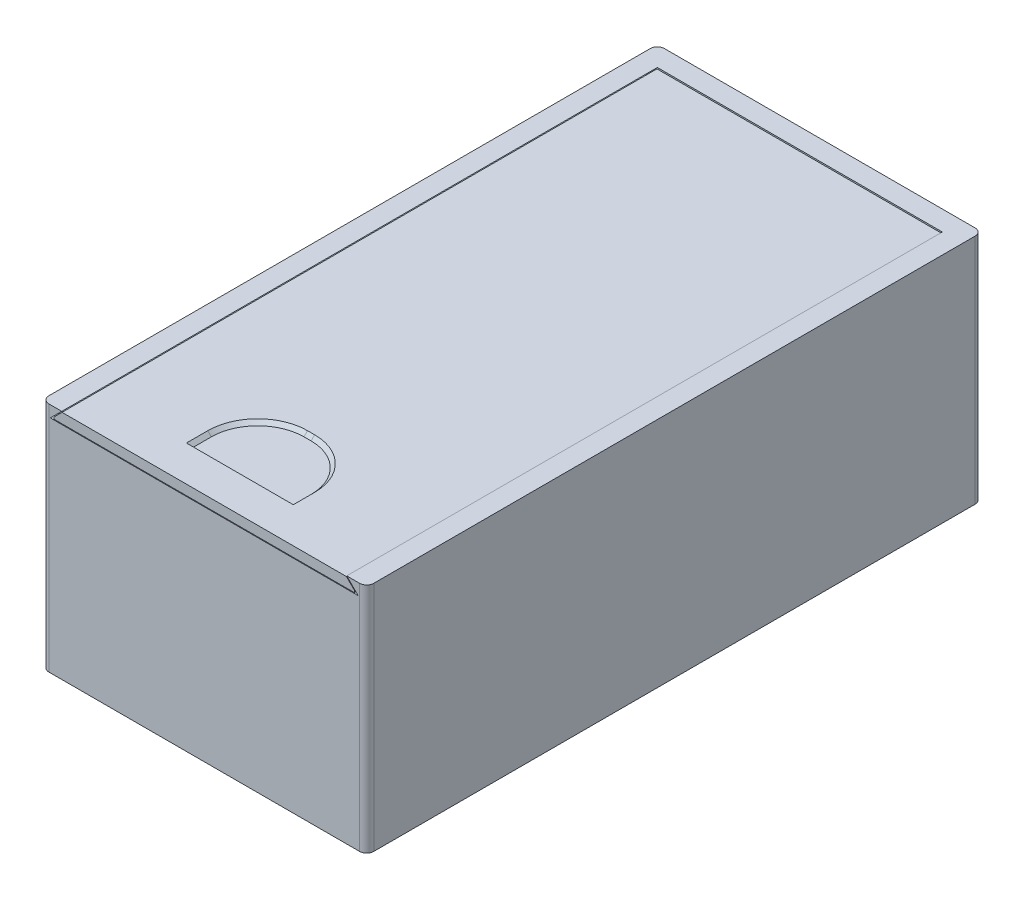
SolidWorks part; units mm, degrees
ref_plane "Front Plane" through (0, 0, 0) normal (0, 0, 1) x (1, 0, 0)
ref_plane "Top Plane" through (0, 0, 0) normal (0, 1, 0) x (1, 0, 0)
ref_plane "Right Plane" through (0, 0, 0) normal (1, 0, 0) x (0, 0, -1)
sketch "Sketch1" plane through (0, 0, 0) normal (0, 0, 1) x (1, 0, 0)
  line L1 (-22.8, -16.3) -> (22.8, -16.3)
  line L2 (-22.8, -16.3) -> (-22.8, 16.3)
  line L3 (-22.8, 16.3) -> (22.8, 16.3)
  line L4 (22.8, -16.3) -> (22.8, 16.3)
  line L5 (-22.8, -16.3) -> (22.8, 16.3) construction
  line L6 (-22.8, 16.3) -> (22.8, -16.3) construction
  point P0 (0, 0)
  dimension "D1" = 32.6
  dimension "D2" = 45.6
extrude "Boss-Extrude1" add sketch "Sketch1" along normal blind 86.4
shell "Shell1" thickness 2.8 removed face at (0, 16.3, 43.2)
sketch "Sketch2" plane through (0, 0, 86.4) normal (0, 0, 1) x (1, 0, 0)
  line L0 (20, 16.3) -> (-20, 16.3) construction
  line L1 (20, 16.3) -> (-20, 16.3)
  line L2 (-20, 16.3) -> (-21.6, 14.7)
  line L3 (-21.6, 14.7) -> (21.6, 14.7)
  line L4 (21.6, 14.7) -> (20, 16.3)
  line L5 (22.8, 16.3) -> (-22.8, 16.3) construction
  line L6 (-22.8, 16.3) -> (-22.8, -16.3) construction
  dimension "D1" = 45
  dimension "D2" = 45
  dimension "D3" = 1.2
extrude "Cut-Extrude1" cut sketch "Sketch2" against normal up to surface (83.6 mm away) up to face at (0, 1.4, 2.8)
sketch "Sketch3" plane through (0, 0, 86.4) normal (0, 0, 1) x (1, 0, 0)
  line L8 (19.9586, 16.2) -> (-19.9586, 16.2)
  line L9 (-19.9586, 16.2) -> (-21.3586, 14.8)
  line L10 (-21.3586, 14.8) -> (21.3586, 14.8)
  line L11 (21.3586, 14.8) -> (19.9586, 16.2)
  line L12 (19.9586, 16.2) -> (-19.9586, 16.2)
  line L13 (-19.9586, 16.2) -> (-21.3586, 14.8)
  line L14 (-21.3586, 14.8) -> (21.3586, 14.8)
  line L15 (21.3586, 14.8) -> (19.9586, 16.2)
  dimension "D1" = 0.1
extrude "Boss-Extrude2" add sketch "Sketch3" against normal offset from surface (83.5 mm away) 0.1 separate body up to face at (0, 8.05, 2.8)
sketch "Sketch5" plane through (0, 16.2, 0) normal (0, 1, 0) x (1, 0, 0)
  line L0 (0, -1118.4) -> (0, 48881.6) construction
  line L1 (19.9586, -86.4) -> (-19.9586, -86.4) construction
  line L3 (-7.5, -81.4) -> (7.5, -81.4)
  line L4 (-7.5, -81.4) -> (-7.5, -71.4)
  line L5 (-7.5, -71.4) -> (7.5, -71.4)
  line L6 (7.5, -81.4) -> (7.5, -71.4)
  line L7 (-7.5, -81.4) -> (7.5, -71.4) construction
  line L8 (-7.5, -71.4) -> (7.5, -81.4) construction
  point P1 (0, -76.4)
  point P5 (0, -86.4)
  dimension "D1" = 5
  dimension "D2" = 15
  dimension "D3" = 10
extrude "Cut-Extrude3" cut sketch "Sketch5" against normal blind 0.5
fillet "Fillet1" radius 7 2 edges at (-7.5, 15.95, 71.4) (7.5, 15.95, 71.4)
chamfer "Chamfer1" distance 0.5 angle 45 5 edges at (7.5, 15.7, 79.9) (5.4497, 15.7, 73.4503) (0, 15.7, 71.4) (-7.5, 15.7, 79.9) (-5.4497, 15.7, 73.4503)
fillet "Fillet2" radius 1 4 edges at (-22.8, 0, 0) (22.8, 0, 0) (-22.8, 0, 86.4) (22.8, 0, 86.4)
sketch "Sketch6" plane through (0, 0, 86.4) normal (0, 0, 1) x (1, 0, 0)
  line L0 (-19.9586, 16.2) -> (-21.3586, 14.8) construction
  line L1 (-21.0586, 15.1) -> (-21.3586, 14.8)
  line L2 (-21.3586, 14.8) -> (21.3586, 14.8) construction
  line L3 (-21.3586, 14.8) -> (-21.0586, 14.8)
  line L4 (-21.0586, 15.1) -> (-21.0586, 14.8)
  line L5 (0, 16.2) -> (0, 14.8) construction
  line L6 (19.9586, 16.2) -> (-19.9586, 16.2) construction
  line L7 (21.0586, 15.1) -> (21.0586, 14.8)
  line L8 (21.3586, 14.8) -> (21.0586, 14.8)
  line L9 (21.0586, 15.1) -> (21.3586, 14.8)
  dimension "D1" = 0.3
extrude "Cut-Extrude4" cut sketch "Sketch6" against normal up to surface (83.5 mm away) up to face at (0, 15.5, 2.9)
equation "\"D1@Boss-Extrude1\"=78+2.8*3"
equation "\"D2@Sketch1\"=40+2.8*2"
equation "\"D1@Sketch1\"=23.00mm+9.6"
